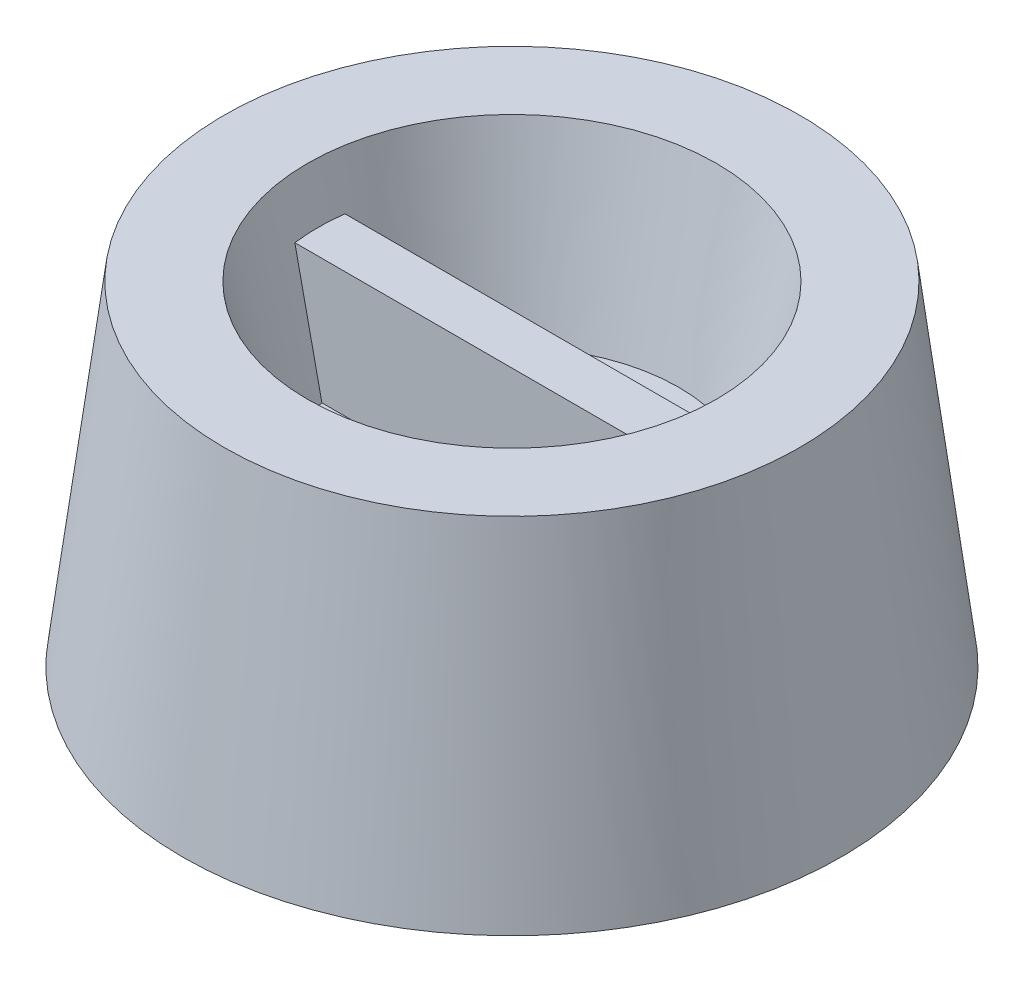
SolidWorks part; units mm, degrees
ref_plane "Front Plane" through (0, 0, 0) normal (0, 0, 1) x (1, 0, 0)
ref_plane "Top Plane" through (0, 0, 0) normal (0, 1, 0) x (1, 0, 0)
ref_plane "Right Plane" through (0, 0, 0) normal (1, 0, 0) x (0, 0, -1)
sketch "Sketch1" plane through (0, 0, 0) normal (0, 1, 0) x (1, 0, 0)
  circle A0 centre (0, 0) radius 7.9
  dimension "D1" = 15.8
ref_plane "Plane1" through (0, 8, 0) normal (0, 1, 0) x (1, 0, 0)
sketch "Sketch2" plane through (0, 8, 0) normal (0, 1, 0) x (1, 0, 0)
  circle A0 centre (0, 0) radius 6.9
  dimension "D1" = 13.8
loft "Loft1" add profiles "Sketch1", "Sketch2" connector at (0, 0, 7.9) connector at (0, 8, 6.9)
sketch "Sketch3" plane through (0, 8, 0) normal (0, 1, 0) x (1, 0, 0)
  circle A0 centre (0, 0) radius 4.9
  dimension "D1" = 9.8
ref_plane "Plane2" through (0, 3.8, 0) normal (0, 1, 0) x (1, 0, 0)
sketch "Sketch4" plane through (0, 3.8, 0) normal (0, 1, 0) x (1, 0, 0)
  circle A0 centre (0, 0) radius 4
  dimension "D1" = 8
loft "Cut-Loft2" cut profiles "Sketch4", "Sketch3" connector at (0, 3.8, 4) connector at (0, 8, 4.9)
ref_plane "Plane3" through (0, 6.8, 0) normal (0, 1, 0) x (1, 0, 0)
sketch "Sketch7" plane through (0, 6.8, 0) normal (0, 1, 0) x (1, 0, 0)
  line L1 (6, -0.6) -> (-6, -0.6)
  line L2 (6, -0.6) -> (6, 0.6)
  line L3 (6, 0.6) -> (-6, 0.6)
  line L4 (-6, -0.6) -> (-6, 0.6)
  line L5 (6, -0.6) -> (-6, 0.6) construction
  line L6 (6, 0.6) -> (-6, -0.6) construction
  point P0 (0, 0)
  dimension "D1" = 1.2
  dimension "D2" = 12
extrude "Boss-Extrude2" add sketch "Sketch7" against normal up to surface (3 mm away) up to face at (0, 3.8, 4)
shell "Shell1" thickness 1.2 removed face at (0, 0, 7.9)
sketch "Sketch8" plane through (0, 2.6, 0) normal (0, -1, 0) x (1, 0, 0)
  circle A0 centre (0, 0) radius 3.95
  circle A1 centre (0, 0) radius 4.9701
  circle M1 centre (0, 0) radius 4.9701
  dimension "D1" = 7.9
extrude "Boss-Extrude3" add sketch "Sketch8" along normal up to surface (2.6 mm away) contours A0 M1 region at (-4.8295, 2.6, 0) up to face at (0, 0, 6.6907)
chamfer "Chamfer1" distance 1.2 angle 20 1 edges at (0, 0, 4.9701) first distance on face at (0, 0, 3.95)
